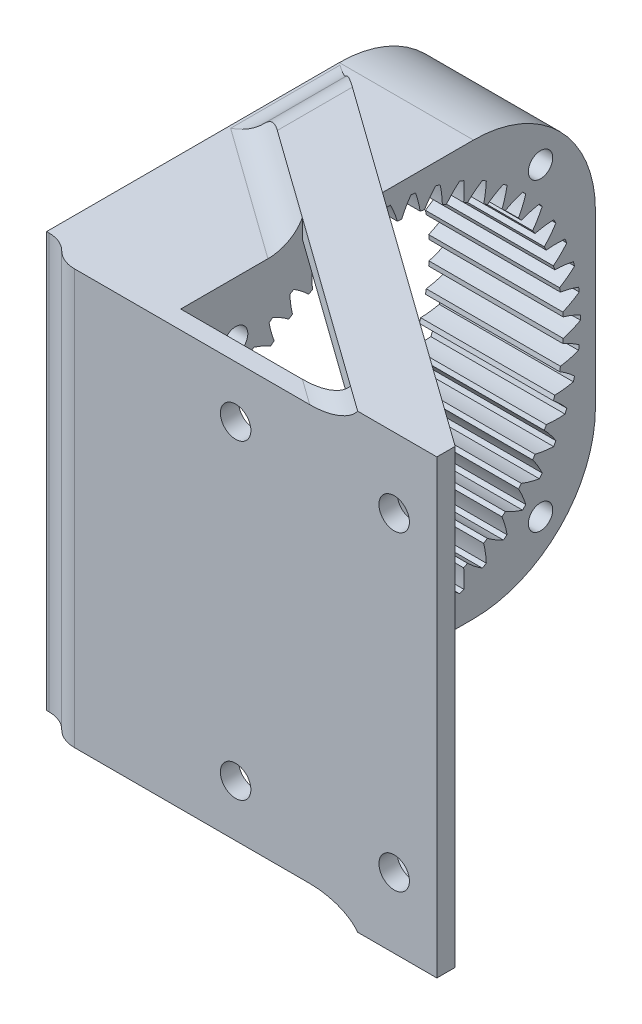
SolidWorks part; units mm, degrees
ref_plane "Plane1" through (0, 0, 0) normal (0, 0, 1) x (1, 0, 0)
ref_plane "Plane2" through (0, 0, 0) normal (0, 1, 0) x (1, 0, 0)
ref_plane "Plane3" through (0, 0, 0) normal (1, 0, 0) x (0, 0, -1)
sketch "HoldingSke" plane through (0, 0, 0) normal (0, 1, 0) x (1, 0, 0)
  line L0 (0, 0) -> (0.5353, -0.5945)
  line L1 (-15, 0) -> (100, 0) construction
  line L2 (0, 0) -> (-2.1039, 2.3779)
  line L3 (0, 0) -> (-11.863, 4.5341)
  line L4 (0, 0) -> (5.7786, 6.4178)
  line L5 (0, 0) -> (-23.7986, -8.8762)
  line L6 (0, 0) -> (-10.5278, -7.1032)
  line L7 (-2.1039, 2.3779) -> (3.3635, 27.1825)
  line L8 (-76.2, 3.6279) -> (-54.61, 3.6279)
  line L9 (-71.009, 38.7566) -> (-53.1078, 45.2721)
  line L10 (-76.2, 71.12) -> (104.1128, 71.12)
  line L11 (0, 0) -> (-12, 0)
  line L12 (-76.2, 101.6) -> (-76.155, 101.6)
  line L13 (24.9733, 27.94) -> (52.9518, 28.4284)
  line L14 (24.9733, 27.94) -> (24.9743, 27.94)
  line L15 (24.9733, 27.94) -> (100.4006, 29.5858)
  circle A0 centre (0, 0) radius 34
  circle A1 centre (0, 0) radius 12.7
  circle A2 centre (0, 0) radius 12.7
  point P27 (0, 0)
  dimension "MHD" = 25.4
  dimension "Hub_dia" = 25.4
  dimension "Diameter" = 68
  dimension "Num_teeth" = 48
  dimension "Pitch" = 0.8
  dimension "Overall_len" = 25.4
  dimension "Show_teeth" = 48
  dimension "Thickness" = 12.7
  dimension "OAL" = 25.4001
  dimension "T_dim" = 21.59
  dimension "Ap" = 20
  dimension "H" = 19.05
  dimension "Pitch_radius" = 180.3128
  dimension "Width" = 12
  dimension "Backlash" = 0.045
  dimension "Addendum_fac" = 1
  dimension "Dedendum_fac" = 1.25
  dimension "Clearance_fac" = 0.25
  dimension "Dedendum_add" = 0.001
  dimension "Module" = 1.25
sketch "BasProSke" plane through (0, 0, 0) normal (0, 1, 0) x (1, 0, 0)
  line L0 (-10, 0) -> (60, 0) construction
  line L1 (0, 28.75) -> (0, 34)
  line L2 (0, 28.75) -> (12, 28.75)
  line L3 (12, 28.75) -> (12, 34)
  line L4 (12, 34) -> (0, 34)
  dimension "Diameter" = 68
  dimension "Thickness" = 12
  dimension "Inside_diameter" = 57.5
revolve "Base-Revolve" add sketch "BasProSke" angle 360 about L0
sketch "TooCutSke" plane through (0, 0, 0) normal (1, 0, 0) x (0, 0, -1)
  line L3 (1.0941, 29.98) -> (1.0941, 53.6633) construction
  line L4 (0, 0) -> (0, 59.563) construction
  line L5 (0, 0) -> (-4.4688, 68.1812) construction
  line L6 (-12.9004, 24.5806) -> (36.1024, 27.7924) construction
  circle A0 centre (0, 0) radius 30 construction
  circle A1 centre (0, 0) radius 31.5635 construction
  circle A2 centre (0, 0) radius 25.3717 construction
  circle A3 centre (0, 0) radius 28.7246 construction
  arc A4 (1.5274, 28.684) -> (0.3763, 31.5613) centre (-12.9004, 24.5806) ccw
  arc A5 (1.5274, 28.684) -> (-1.5274, 28.684) centre (0, 0) ccw
  arc A6 (0.3763, 31.5613) -> (-0.3763, 31.5613) centre (0, 0) ccw
  arc A7 (-0.3763, 31.5613) -> (-1.5274, 28.684) centre (12.9004, 24.5806) ccw
  dimension "Pitch_dia" = 60
  dimension "Base_dia" = 50.7434
  dimension "Root_dia" = 63.127
  dimension "Overcut_dia" = 57.4492
  dimension "Flank_rad" = 15
  dimension "Half_ang" = 3.75
  dimension "Half_CT" = 1.0941
extrude "ToothCut" cut sketch "TooCutSke" along normal through all
fillet "Breaks" [suppressed] radius 0.125
fillet "RootFillets" [suppressed] radius 0.3135
pattern_circular "TeethCuts" count 48 every 7.5 about axis through (-10, 0, 0) along (1, 0, 0) of "RootFillets", "Breaks", "ToothCut"
sketch "Sketch1" plane through (0, 0, 0) normal (-1, 0, 0) x (0, 0, 1)
  line L1 (-34, -34) -> (34, -34)
  line L2 (-34, -34) -> (-34, 34)
  line L3 (-34, 34) -> (34, 34)
  line L4 (34, -34) -> (34, 34)
  line L5 (-34, -34) -> (34, 34) construction
  line L6 (-34, 34) -> (34, -34) construction
  circle A0 centre (0, 0) radius 34 construction
  circle A1 centre (0, 0) radius 34
  point P0 (0, 0)
extrude "Boss-Extrude1" add sketch "Sketch1" against normal up to surface (12 mm away) contours A1 L4 L3 | A1 L3 L2 | A1 L1 L4 | A1 L2 L1 region at (0, -26.4055, -26.4055) region at (0, -26.4055, 26.4055) region at (0, 26.4055, -26.4055) region at (0, 26.4055, 26.4055) up to face at (12, 0, 34)
sketch "Sketch3" plane through (12, 0, 0) normal (1, 0, 0) x (0, 0, -1)
  line L0 (-34, 34) -> (34, 34) construction
  line L1 (25, -25) -> (-25, -25) construction
  line L2 (25, -25) -> (25, 25) construction
  line L3 (25, 25) -> (-25, 25) construction
  line L4 (-25, -25) -> (-25, 25) construction
  line L5 (25, -25) -> (-25, 25) construction
  line L6 (25, 25) -> (-25, -25) construction
  circle A0 centre (-25, -25) radius 2
  circle A1 centre (-25, 25) radius 2
  circle A2 centre (25, 25) radius 2
  circle A3 centre (25, -25) radius 2
  point P0 (0, 0)
  dimension "D2" = 4
  dimension "D1" = 9
extrude "Cut-Extrude1" cut sketch "Sketch3" against normal through all
sketch "Sketch4" plane through (12, 0, 0) normal (1, 0, 0) x (0, 0, -1)
  line L1 (-34, -34) -> (34, -34)
  line L2 (-34, -34) -> (-34, 34)
  line L3 (-34, 34) -> (34, 34)
  line L4 (34, -34) -> (34, 34)
  circle A1 centre (-25, -25) radius 2
  circle A2 centre (-25, -25) radius 2
  circle A3 centre (-25, 25) radius 2
  circle A4 centre (-25, 25) radius 2
  circle A5 centre (25, 25) radius 2
  circle A6 centre (25, 25) radius 2
  circle A7 centre (25, -25) radius 2
  circle A8 centre (25, -25) radius 2
  arc A192 (3.7465, 31.3404) -> (2.2403, 28.6626) centre (15.9985, 22.6865) ccw
  arc A193 (4.4926, 31.2421) -> (3.7465, 31.3404) centre (0, 0) ccw
  arc A194 (5.2544, 28.2658) -> (4.4926, 31.2421) centre (-9.5817, 26.0542) ccw
  arc A195 (5.9624, 28.1249) -> (5.2544, 28.2658) centre (0, 0) ccw
  arc A196 (7.8052, 30.5832) -> (5.9624, 28.1249) centre (18.8228, 20.4042) ccw
  arc A197 (8.5321, 30.3885) -> (7.8052, 30.5832) centre (0, 0) ccw
  arc A198 (8.8989, 27.3381) -> (8.5321, 30.3885) centre (-6.0989, 27.0819) ccw
  arc A199 (9.5824, 27.1061) -> (8.8989, 27.3381) centre (0, 0) ccw
  arc A200 (11.7304, 29.3028) -> (9.5824, 27.1061) centre (21.325, 17.7727) ccw
  arc A201 (12.4256, 29.0148) -> (11.7304, 29.3028) centre (0, 0) ccw
  arc A202 (12.3911, 25.9427) -> (12.4256, 29.0148) centre (-2.5119, 27.6463) ccw
  arc A203 (13.0385, 25.6234) -> (12.3911, 25.9427) centre (0, 0) ccw
  arc A204 (15.4548, 27.521) -> (13.0385, 25.6234) centre (23.4624, 14.8372) ccw
  arc A205 (16.1065, 27.1447) -> (15.4548, 27.521) centre (0, 0) ccw
  arc A206 (15.6713, 24.1034) -> (16.1065, 27.1447) centre (1.1182, 27.7376) ccw
  arc A207 (16.2715, 23.7023) -> (15.6713, 24.1034) centre (0, 0) ccw
  arc A208 (18.9148, 25.2683) -> (16.2715, 23.7023) centre (25.1983, 11.6478) ccw
  arc A209 (19.5118, 24.8102) -> (18.9148, 25.2683) centre (0, 0) ccw
  arc A210 (18.6833, 21.8517) -> (19.5118, 24.8102) centre (4.7291, 27.3544) ccw
  arc A211 (19.2261, 21.3757) -> (18.6833, 21.8517) centre (0, 0) ccw
  arc A212 (22.0511, 22.5832) -> (19.2261, 21.3757) centre (26.5031, 8.2591) ccw
  arc A213 (22.5832, 22.0511) -> (22.0511, 22.5832) centre (0, 0) ccw
  arc A214 (21.3757, 19.2261) -> (22.5832, 22.0511) centre (8.2591, 26.5031) ccw
  arc A215 (21.8517, 18.6833) -> (21.3757, 19.2261) centre (0, 0) ccw
  arc A216 (24.8102, 19.5118) -> (21.8517, 18.6833) centre (27.3544, 4.7291) ccw
  arc A217 (25.2683, 18.9148) -> (24.8102, 19.5118) centre (0, 0) ccw
  arc A218 (23.7023, 16.2715) -> (25.2683, 18.9148) centre (11.6478, 25.1983) ccw
  arc A219 (24.1034, 15.6713) -> (23.7023, 16.2715) centre (0, 0) ccw
  arc A220 (27.1447, 16.1065) -> (24.1034, 15.6713) centre (27.7376, 1.1182) ccw
  arc A221 (27.521, 15.4548) -> (27.1447, 16.1065) centre (0, 0) ccw
  arc A222 (25.6234, 13.0385) -> (27.521, 15.4548) centre (14.8372, 23.4624) ccw
  arc A223 (25.9427, 12.3911) -> (25.6234, 13.0385) centre (0, 0) ccw
  arc A224 (29.0148, 12.4256) -> (25.9427, 12.3911) centre (27.6463, -2.5119) ccw
  arc A225 (29.3028, 11.7304) -> (29.0148, 12.4256) centre (0, 0) ccw
  arc A226 (27.1061, 9.5824) -> (29.3028, 11.7304) centre (17.7727, 21.325) ccw
  arc A227 (27.3381, 8.8989) -> (27.1061, 9.5824) centre (0, 0) ccw
  arc A228 (30.3885, 8.5321) -> (27.3381, 8.8989) centre (27.0819, -6.0989) ccw
  arc A229 (30.5832, 7.8052) -> (30.3885, 8.5321) centre (0, 0) ccw
  arc A230 (28.1249, 5.9624) -> (30.5832, 7.8052) centre (20.4042, 18.8228) ccw
  arc A231 (28.2658, 5.2544) -> (28.1249, 5.9624) centre (0, 0) ccw
  arc A232 (31.2421, 4.4926) -> (28.2658, 5.2544) centre (26.0542, -9.5817) ccw
  arc A233 (31.3404, 3.7465) -> (31.2421, 4.4926) centre (0, 0) ccw
  arc A234 (28.6626, 2.2403) -> (31.3404, 3.7465) centre (22.6865, 15.9985) ccw
  arc A235 (28.7098, 1.52) -> (28.6626, 2.2403) centre (0, 0) ccw
  arc A236 (31.5613, 0.3763) -> (28.7098, 1.52) centre (24.5806, -12.9004) ccw
  arc A237 (31.5613, -0.3763) -> (31.5613, 0.3763) centre (0, 0) ccw
  arc A238 (28.7098, -1.52) -> (31.5613, -0.3763) centre (24.5806, 12.9004) ccw
  arc A239 (28.6626, -2.2403) -> (28.7098, -1.52) centre (0, 0) ccw
  arc A240 (31.3404, -3.7465) -> (28.6626, -2.2403) centre (22.6865, -15.9985) ccw
  arc A241 (31.2421, -4.4926) -> (31.3404, -3.7465) centre (0, 0) ccw
  arc A242 (28.2658, -5.2544) -> (31.2421, -4.4926) centre (26.0542, 9.5817) ccw
  arc A243 (28.1249, -5.9624) -> (28.2658, -5.2544) centre (0, 0) ccw
  arc A244 (30.5832, -7.8052) -> (28.1249, -5.9624) centre (20.4042, -18.8228) ccw
  arc A245 (30.3885, -8.5321) -> (30.5832, -7.8052) centre (0, 0) ccw
  arc A246 (27.3381, -8.8989) -> (30.3885, -8.5321) centre (27.0819, 6.0989) ccw
  arc A247 (27.1061, -9.5824) -> (27.3381, -8.8989) centre (0, 0) ccw
  arc A248 (29.3028, -11.7304) -> (27.1061, -9.5824) centre (17.7727, -21.325) ccw
  arc A249 (29.0148, -12.4256) -> (29.3028, -11.7304) centre (0, 0) ccw
  arc A250 (25.9427, -12.3911) -> (29.0148, -12.4256) centre (27.6463, 2.5119) ccw
  arc A251 (25.6234, -13.0385) -> (25.9427, -12.3911) centre (0, 0) ccw
  arc A252 (27.521, -15.4548) -> (25.6234, -13.0385) centre (14.8372, -23.4624) ccw
  arc A253 (27.1447, -16.1065) -> (27.521, -15.4548) centre (0, 0) ccw
  arc A254 (24.1034, -15.6713) -> (27.1447, -16.1065) centre (27.7376, -1.1182) ccw
  arc A255 (23.7023, -16.2715) -> (24.1034, -15.6713) centre (0, 0) ccw
  arc A256 (25.2683, -18.9148) -> (23.7023, -16.2715) centre (11.6478, -25.1983) ccw
  arc A257 (24.8102, -19.5118) -> (25.2683, -18.9148) centre (0, 0) ccw
  arc A258 (21.8517, -18.6833) -> (24.8102, -19.5118) centre (27.3544, -4.7291) ccw
  arc A259 (21.3757, -19.2261) -> (21.8517, -18.6833) centre (0, 0) ccw
  arc A260 (22.5832, -22.0511) -> (21.3757, -19.2261) centre (8.2591, -26.5031) ccw
  arc A261 (22.0511, -22.5832) -> (22.5832, -22.0511) centre (0, 0) ccw
  arc A262 (19.2261, -21.3757) -> (22.0511, -22.5832) centre (26.5031, -8.2591) ccw
  arc A263 (18.6833, -21.8517) -> (19.2261, -21.3757) centre (0, 0) ccw
  arc A264 (19.5118, -24.8102) -> (18.6833, -21.8517) centre (4.7291, -27.3544) ccw
  arc A265 (18.9148, -25.2683) -> (19.5118, -24.8102) centre (0, 0) ccw
  arc A266 (16.2715, -23.7023) -> (18.9148, -25.2683) centre (25.1983, -11.6478) ccw
  arc A267 (15.6713, -24.1034) -> (16.2715, -23.7023) centre (0, 0) ccw
  arc A268 (16.1065, -27.1447) -> (15.6713, -24.1034) centre (1.1182, -27.7376) ccw
  arc A269 (15.4548, -27.521) -> (16.1065, -27.1447) centre (0, 0) ccw
  arc A270 (13.0385, -25.6234) -> (15.4548, -27.521) centre (23.4624, -14.8372) ccw
  arc A271 (12.3911, -25.9427) -> (13.0385, -25.6234) centre (0, 0) ccw
  arc A272 (12.4256, -29.0148) -> (12.3911, -25.9427) centre (-2.5119, -27.6463) ccw
  arc A273 (11.7304, -29.3028) -> (12.4256, -29.0148) centre (0, 0) ccw
  arc A274 (9.5824, -27.1061) -> (11.7304, -29.3028) centre (21.325, -17.7727) ccw
  arc A275 (8.8989, -27.3381) -> (9.5824, -27.1061) centre (0, 0) ccw
  arc A276 (8.5321, -30.3885) -> (8.8989, -27.3381) centre (-6.0989, -27.0819) ccw
  arc A277 (7.8052, -30.5832) -> (8.5321, -30.3885) centre (0, 0) ccw
  arc A278 (5.9624, -28.1249) -> (7.8052, -30.5832) centre (18.8228, -20.4042) ccw
  arc A279 (5.2544, -28.2658) -> (5.9624, -28.1249) centre (0, 0) ccw
  arc A280 (4.4926, -31.2421) -> (5.2544, -28.2658) centre (-9.5817, -26.0542) ccw
  arc A281 (3.7465, -31.3404) -> (4.4926, -31.2421) centre (0, 0) ccw
  arc A282 (2.2403, -28.6626) -> (3.7465, -31.3404) centre (15.9985, -22.6865) ccw
  arc A283 (1.52, -28.7098) -> (2.2403, -28.6626) centre (0, 0) ccw
  arc A284 (0.3763, -31.5613) -> (1.52, -28.7098) centre (-12.9004, -24.5806) ccw
  arc A285 (-0.3763, -31.5613) -> (0.3763, -31.5613) centre (0, 0) ccw
  arc A286 (-1.52, -28.7098) -> (-0.3763, -31.5613) centre (12.9004, -24.5806) ccw
  arc A287 (-2.2403, -28.6626) -> (-1.52, -28.7098) centre (0, 0) ccw
  arc A288 (-3.7465, -31.3404) -> (-2.2403, -28.6626) centre (-15.9985, -22.6865) ccw
  arc A289 (-4.4926, -31.2421) -> (-3.7465, -31.3404) centre (0, 0) ccw
  arc A290 (-5.2544, -28.2658) -> (-4.4926, -31.2421) centre (9.5817, -26.0542) ccw
  arc A291 (-5.9624, -28.1249) -> (-5.2544, -28.2658) centre (0, 0) ccw
  arc A292 (-7.8052, -30.5832) -> (-5.9624, -28.1249) centre (-18.8228, -20.4042) ccw
  arc A293 (-8.5321, -30.3885) -> (-7.8052, -30.5832) centre (0, 0) ccw
  arc A294 (-8.8989, -27.3381) -> (-8.5321, -30.3885) centre (6.0989, -27.0819) ccw
  arc A295 (-9.5824, -27.1061) -> (-8.8989, -27.3381) centre (0, 0) ccw
  arc A296 (-11.7304, -29.3028) -> (-9.5824, -27.1061) centre (-21.325, -17.7727) ccw
  arc A297 (-12.4256, -29.0148) -> (-11.7304, -29.3028) centre (0, 0) ccw
  arc A298 (-12.3911, -25.9427) -> (-12.4256, -29.0148) centre (2.5119, -27.6463) ccw
  arc A299 (-13.0385, -25.6234) -> (-12.3911, -25.9427) centre (0, 0) ccw
  arc A300 (-15.4548, -27.521) -> (-13.0385, -25.6234) centre (-23.4624, -14.8372) ccw
  arc A301 (-16.1065, -27.1447) -> (-15.4548, -27.521) centre (0, 0) ccw
  arc A302 (-15.6713, -24.1034) -> (-16.1065, -27.1447) centre (-1.1182, -27.7376) ccw
  arc A303 (-16.2715, -23.7023) -> (-15.6713, -24.1034) centre (0, 0) ccw
  arc A304 (-18.9148, -25.2683) -> (-16.2715, -23.7023) centre (-25.1983, -11.6478) ccw
  arc A305 (-19.5118, -24.8102) -> (-18.9148, -25.2683) centre (0, 0) ccw
  arc A306 (-18.6833, -21.8517) -> (-19.5118, -24.8102) centre (-4.7291, -27.3544) ccw
  arc A307 (-19.2261, -21.3757) -> (-18.6833, -21.8517) centre (0, 0) ccw
  arc A308 (-22.0511, -22.5832) -> (-19.2261, -21.3757) centre (-26.5031, -8.2591) ccw
  arc A309 (-22.5832, -22.0511) -> (-22.0511, -22.5832) centre (0, 0) ccw
  arc A310 (-21.3757, -19.2261) -> (-22.5832, -22.0511) centre (-8.2591, -26.5031) ccw
  arc A311 (-21.8517, -18.6833) -> (-21.3757, -19.2261) centre (0, 0) ccw
  arc A312 (-24.8102, -19.5118) -> (-21.8517, -18.6833) centre (-27.3544, -4.7291) ccw
  arc A313 (-25.2683, -18.9148) -> (-24.8102, -19.5118) centre (0, 0) ccw
  arc A314 (-23.7023, -16.2715) -> (-25.2683, -18.9148) centre (-11.6478, -25.1983) ccw
  arc A315 (-24.1034, -15.6713) -> (-23.7023, -16.2715) centre (0, 0) ccw
  arc A316 (-27.1447, -16.1065) -> (-24.1034, -15.6713) centre (-27.7376, -1.1182) ccw
  arc A317 (-27.521, -15.4548) -> (-27.1447, -16.1065) centre (0, 0) ccw
  arc A318 (-25.6234, -13.0385) -> (-27.521, -15.4548) centre (-14.8372, -23.4624) ccw
  arc A319 (-25.9427, -12.3911) -> (-25.6234, -13.0385) centre (0, 0) ccw
  arc A320 (-29.0148, -12.4256) -> (-25.9427, -12.3911) centre (-27.6463, 2.5119) ccw
  arc A321 (-29.3028, -11.7304) -> (-29.0148, -12.4256) centre (0, 0) ccw
  arc A322 (-27.1061, -9.5824) -> (-29.3028, -11.7304) centre (-17.7727, -21.325) ccw
  arc A323 (-27.3381, -8.8989) -> (-27.1061, -9.5824) centre (0, 0) ccw
  arc A324 (-30.3885, -8.5321) -> (-27.3381, -8.8989) centre (-27.0819, 6.0989) ccw
  arc A325 (-30.5832, -7.8052) -> (-30.3885, -8.5321) centre (0, 0) ccw
  arc A326 (-28.1249, -5.9624) -> (-30.5832, -7.8052) centre (-20.4042, -18.8228) ccw
  arc A327 (-28.2658, -5.2544) -> (-28.1249, -5.9624) centre (0, 0) ccw
  arc A328 (-31.2421, -4.4926) -> (-28.2658, -5.2544) centre (-26.0542, 9.5817) ccw
  arc A329 (-31.3404, -3.7465) -> (-31.2421, -4.4926) centre (0, 0) ccw
  arc A330 (-28.6626, -2.2403) -> (-31.3404, -3.7465) centre (-22.6865, -15.9985) ccw
  arc A331 (-28.7098, -1.52) -> (-28.6626, -2.2403) centre (0, 0) ccw
  arc A332 (-31.5613, -0.3763) -> (-28.7098, -1.52) centre (-24.5806, 12.9004) ccw
  arc A333 (-31.5613, 0.3763) -> (-31.5613, -0.3763) centre (0, 0) ccw
  arc A334 (-28.7098, 1.52) -> (-31.5613, 0.3763) centre (-24.5806, -12.9004) ccw
  arc A335 (-28.6626, 2.2403) -> (-28.7098, 1.52) centre (0, 0) ccw
  arc A336 (-31.3404, 3.7465) -> (-28.6626, 2.2403) centre (-22.6865, 15.9985) ccw
  arc A337 (-31.2421, 4.4926) -> (-31.3404, 3.7465) centre (0, 0) ccw
  arc A338 (-28.2658, 5.2544) -> (-31.2421, 4.4926) centre (-26.0542, -9.5817) ccw
  arc A339 (-28.1249, 5.9624) -> (-28.2658, 5.2544) centre (0, 0) ccw
  arc A340 (-30.5832, 7.8052) -> (-28.1249, 5.9624) centre (-20.4042, 18.8228) ccw
  arc A341 (-30.3885, 8.5321) -> (-30.5832, 7.8052) centre (0, 0) ccw
  arc A342 (-27.3381, 8.8989) -> (-30.3885, 8.5321) centre (-27.0819, -6.0989) ccw
  arc A343 (-27.1061, 9.5824) -> (-27.3381, 8.8989) centre (0, 0) ccw
  arc A344 (-29.3028, 11.7304) -> (-27.1061, 9.5824) centre (-17.7727, 21.325) ccw
  arc A345 (-29.0148, 12.4256) -> (-29.3028, 11.7304) centre (0, 0) ccw
  arc A346 (-25.9427, 12.3911) -> (-29.0148, 12.4256) centre (-27.6463, -2.5119) ccw
  arc A347 (-25.6234, 13.0385) -> (-25.9427, 12.3911) centre (0, 0) ccw
  arc A348 (-27.521, 15.4548) -> (-25.6234, 13.0385) centre (-14.8372, 23.4624) ccw
  arc A349 (-27.1447, 16.1065) -> (-27.521, 15.4548) centre (0, 0) ccw
  arc A350 (-24.1034, 15.6713) -> (-27.1447, 16.1065) centre (-27.7376, 1.1182) ccw
  arc A351 (-23.7023, 16.2715) -> (-24.1034, 15.6713) centre (0, 0) ccw
  arc A352 (-25.2683, 18.9148) -> (-23.7023, 16.2715) centre (-11.6478, 25.1983) ccw
  arc A353 (-24.8102, 19.5118) -> (-25.2683, 18.9148) centre (0, 0) ccw
  arc A354 (-21.8517, 18.6833) -> (-24.8102, 19.5118) centre (-27.3544, 4.7291) ccw
  arc A355 (-21.3757, 19.2261) -> (-21.8517, 18.6833) centre (0, 0) ccw
  arc A356 (-22.5832, 22.0511) -> (-21.3757, 19.2261) centre (-8.2591, 26.5031) ccw
  arc A357 (-22.0511, 22.5832) -> (-22.5832, 22.0511) centre (0, 0) ccw
  arc A358 (-19.2261, 21.3757) -> (-22.0511, 22.5832) centre (-26.5031, 8.2591) ccw
  arc A359 (-18.6833, 21.8517) -> (-19.2261, 21.3757) centre (0, 0) ccw
  arc A360 (-19.5118, 24.8102) -> (-18.6833, 21.8517) centre (-4.7291, 27.3544) ccw
  arc A361 (-18.9148, 25.2683) -> (-19.5118, 24.8102) centre (0, 0) ccw
  arc A362 (-16.2715, 23.7023) -> (-18.9148, 25.2683) centre (-25.1983, 11.6478) ccw
  arc A363 (-15.6713, 24.1034) -> (-16.2715, 23.7023) centre (0, 0) ccw
  arc A364 (-16.1065, 27.1447) -> (-15.6713, 24.1034) centre (-1.1182, 27.7376) ccw
  arc A365 (-15.4548, 27.521) -> (-16.1065, 27.1447) centre (0, 0) ccw
  arc A366 (-13.0385, 25.6234) -> (-15.4548, 27.521) centre (-23.4624, 14.8372) ccw
  arc A367 (-12.3911, 25.9427) -> (-13.0385, 25.6234) centre (0, 0) ccw
  arc A368 (-12.4256, 29.0148) -> (-12.3911, 25.9427) centre (2.5119, 27.6463) ccw
  arc A369 (-11.7304, 29.3028) -> (-12.4256, 29.0148) centre (0, 0) ccw
  arc A370 (-9.5824, 27.1061) -> (-11.7304, 29.3028) centre (-21.325, 17.7727) ccw
  arc A371 (-8.8989, 27.3381) -> (-9.5824, 27.1061) centre (0, 0) ccw
  arc A372 (-8.5321, 30.3885) -> (-8.8989, 27.3381) centre (6.0989, 27.0819) ccw
  arc A373 (-7.8052, 30.5832) -> (-8.5321, 30.3885) centre (0, 0) ccw
  arc A374 (-5.9624, 28.1249) -> (-7.8052, 30.5832) centre (-18.8228, 20.4042) ccw
  arc A375 (-5.2544, 28.2658) -> (-5.9624, 28.1249) centre (0, 0) ccw
  arc A376 (-4.4926, 31.2421) -> (-5.2544, 28.2658) centre (9.5817, 26.0542) ccw
  arc A377 (-3.7465, 31.3404) -> (-4.4926, 31.2421) centre (0, 0) ccw
  arc A378 (-2.2403, 28.6626) -> (-3.7465, 31.3404) centre (-15.9985, 22.6865) ccw
  arc A379 (-1.52, 28.7098) -> (-2.2403, 28.6626) centre (0, 0) ccw
  arc A380 (-0.3763, 31.5613) -> (-1.52, 28.7098) centre (12.9004, 24.5806) ccw
  arc A381 (0.3763, 31.5613) -> (-0.3763, 31.5613) centre (0, 0) ccw
  arc A382 (1.52, 28.7098) -> (0.3763, 31.5613) centre (-12.9004, 24.5806) ccw
  arc A383 (2.2403, 28.6626) -> (1.52, 28.7098) centre (0, 0) ccw
  arc A384 (3.7465, 31.3404) -> (2.2403, 28.6626) centre (15.9985, 22.6865) ccw
  arc A385 (4.4926, 31.2421) -> (3.7465, 31.3404) centre (0, 0) ccw
  arc A386 (5.2544, 28.2658) -> (4.4926, 31.2421) centre (-9.5817, 26.0542) ccw
  arc A387 (5.9624, 28.1249) -> (5.2544, 28.2658) centre (0, 0) ccw
  arc A388 (7.8052, 30.5832) -> (5.9624, 28.1249) centre (18.8228, 20.4042) ccw
  arc A389 (8.5321, 30.3885) -> (7.8052, 30.5832) centre (0, 0) ccw
  arc A390 (8.8989, 27.3381) -> (8.5321, 30.3885) centre (-6.0989, 27.0819) ccw
  arc A391 (9.5824, 27.1061) -> (8.8989, 27.3381) centre (0, 0) ccw
  arc A392 (11.7304, 29.3028) -> (9.5824, 27.1061) centre (21.325, 17.7727) ccw
  arc A393 (12.4256, 29.0148) -> (11.7304, 29.3028) centre (0, 0) ccw
  arc A394 (12.3911, 25.9427) -> (12.4256, 29.0148) centre (-2.5119, 27.6463) ccw
  arc A395 (13.0385, 25.6234) -> (12.3911, 25.9427) centre (0, 0) ccw
  arc A396 (15.4548, 27.521) -> (13.0385, 25.6234) centre (23.4624, 14.8372) ccw
  arc A397 (16.1065, 27.1447) -> (15.4548, 27.521) centre (0, 0) ccw
  arc A398 (15.6713, 24.1034) -> (16.1065, 27.1447) centre (1.1182, 27.7376) ccw
  arc A399 (16.2715, 23.7023) -> (15.6713, 24.1034) centre (0, 0) ccw
  arc A400 (18.9148, 25.2683) -> (16.2715, 23.7023) centre (25.1983, 11.6478) ccw
  arc A401 (19.5118, 24.8102) -> (18.9148, 25.2683) centre (0, 0) ccw
  arc A402 (18.6833, 21.8517) -> (19.5118, 24.8102) centre (4.7291, 27.3544) ccw
  arc A403 (19.2261, 21.3757) -> (18.6833, 21.8517) centre (0, 0) ccw
  arc A404 (22.0511, 22.5832) -> (19.2261, 21.3757) centre (26.5031, 8.2591) ccw
  arc A405 (22.5832, 22.0511) -> (22.0511, 22.5832) centre (0, 0) ccw
  arc A406 (21.3757, 19.2261) -> (22.5832, 22.0511) centre (8.2591, 26.5031) ccw
  arc A407 (21.8517, 18.6833) -> (21.3757, 19.2261) centre (0, 0) ccw
  arc A408 (24.8102, 19.5118) -> (21.8517, 18.6833) centre (27.3544, 4.7291) ccw
  arc A409 (25.2683, 18.9148) -> (24.8102, 19.5118) centre (0, 0) ccw
  arc A410 (23.7023, 16.2715) -> (25.2683, 18.9148) centre (11.6478, 25.1983) ccw
  arc A411 (24.1034, 15.6713) -> (23.7023, 16.2715) centre (0, 0) ccw
  arc A412 (27.1447, 16.1065) -> (24.1034, 15.6713) centre (27.7376, 1.1182) ccw
  arc A413 (27.521, 15.4548) -> (27.1447, 16.1065) centre (0, 0) ccw
  arc A414 (25.6234, 13.0385) -> (27.521, 15.4548) centre (14.8372, 23.4624) ccw
  arc A415 (25.9427, 12.3911) -> (25.6234, 13.0385) centre (0, 0) ccw
  arc A416 (29.0148, 12.4256) -> (25.9427, 12.3911) centre (27.6463, -2.5119) ccw
  arc A417 (29.3028, 11.7304) -> (29.0148, 12.4256) centre (0, 0) ccw
  arc A418 (27.1061, 9.5824) -> (29.3028, 11.7304) centre (17.7727, 21.325) ccw
  arc A419 (27.3381, 8.8989) -> (27.1061, 9.5824) centre (0, 0) ccw
  arc A420 (30.3885, 8.5321) -> (27.3381, 8.8989) centre (27.0819, -6.0989) ccw
  arc A421 (30.5832, 7.8052) -> (30.3885, 8.5321) centre (0, 0) ccw
  arc A422 (28.1249, 5.9624) -> (30.5832, 7.8052) centre (20.4042, 18.8228) ccw
  arc A423 (28.2658, 5.2544) -> (28.1249, 5.9624) centre (0, 0) ccw
  arc A424 (31.2421, 4.4926) -> (28.2658, 5.2544) centre (26.0542, -9.5817) ccw
  arc A425 (31.3404, 3.7465) -> (31.2421, 4.4926) centre (0, 0) ccw
  arc A426 (28.6626, 2.2403) -> (31.3404, 3.7465) centre (22.6865, 15.9985) ccw
  arc A427 (28.7098, 1.52) -> (28.6626, 2.2403) centre (0, 0) ccw
  arc A428 (31.5613, 0.3763) -> (28.7098, 1.52) centre (24.5806, -12.9004) ccw
  arc A429 (31.5613, -0.3763) -> (31.5613, 0.3763) centre (0, 0) ccw
  arc A430 (28.7098, -1.52) -> (31.5613, -0.3763) centre (24.5806, 12.9004) ccw
  arc A431 (28.6626, -2.2403) -> (28.7098, -1.52) centre (0, 0) ccw
  arc A432 (31.3404, -3.7465) -> (28.6626, -2.2403) centre (22.6865, -15.9985) ccw
  arc A433 (31.2421, -4.4926) -> (31.3404, -3.7465) centre (0, 0) ccw
  arc A434 (28.2658, -5.2544) -> (31.2421, -4.4926) centre (26.0542, 9.5817) ccw
  arc A435 (28.1249, -5.9624) -> (28.2658, -5.2544) centre (0, 0) ccw
  arc A436 (30.5832, -7.8052) -> (28.1249, -5.9624) centre (20.4042, -18.8228) ccw
  arc A437 (30.3885, -8.5321) -> (30.5832, -7.8052) centre (0, 0) ccw
  arc A438 (27.3381, -8.8989) -> (30.3885, -8.5321) centre (27.0819, 6.0989) ccw
  arc A439 (27.1061, -9.5824) -> (27.3381, -8.8989) centre (0, 0) ccw
  arc A440 (29.3028, -11.7304) -> (27.1061, -9.5824) centre (17.7727, -21.325) ccw
  arc A441 (29.0148, -12.4256) -> (29.3028, -11.7304) centre (0, 0) ccw
  arc A442 (25.9427, -12.3911) -> (29.0148, -12.4256) centre (27.6463, 2.5119) ccw
  arc A443 (25.6234, -13.0385) -> (25.9427, -12.3911) centre (0, 0) ccw
  arc A444 (27.521, -15.4548) -> (25.6234, -13.0385) centre (14.8372, -23.4624) ccw
  arc A445 (27.1447, -16.1065) -> (27.521, -15.4548) centre (0, 0) ccw
  arc A446 (24.1034, -15.6713) -> (27.1447, -16.1065) centre (27.7376, -1.1182) ccw
  arc A447 (23.7023, -16.2715) -> (24.1034, -15.6713) centre (0, 0) ccw
  arc A448 (25.2683, -18.9148) -> (23.7023, -16.2715) centre (11.6478, -25.1983) ccw
  arc A449 (24.8102, -19.5118) -> (25.2683, -18.9148) centre (0, 0) ccw
  arc A450 (21.8517, -18.6833) -> (24.8102, -19.5118) centre (27.3544, -4.7291) ccw
  arc A451 (21.3757, -19.2261) -> (21.8517, -18.6833) centre (0, 0) ccw
  arc A452 (22.5832, -22.0511) -> (21.3757, -19.2261) centre (8.2591, -26.5031) ccw
  arc A453 (22.0511, -22.5832) -> (22.5832, -22.0511) centre (0, 0) ccw
  arc A454 (19.2261, -21.3757) -> (22.0511, -22.5832) centre (26.5031, -8.2591) ccw
  arc A455 (18.6833, -21.8517) -> (19.2261, -21.3757) centre (0, 0) ccw
  arc A456 (19.5118, -24.8102) -> (18.6833, -21.8517) centre (4.7291, -27.3544) ccw
  arc A457 (18.9148, -25.2683) -> (19.5118, -24.8102) centre (0, 0) ccw
  arc A458 (16.2715, -23.7023) -> (18.9148, -25.2683) centre (25.1983, -11.6478) ccw
  arc A459 (15.6713, -24.1034) -> (16.2715, -23.7023) centre (0, 0) ccw
  arc A460 (16.1065, -27.1447) -> (15.6713, -24.1034) centre (1.1182, -27.7376) ccw
  arc A461 (15.4548, -27.521) -> (16.1065, -27.1447) centre (0, 0) ccw
  arc A462 (13.0385, -25.6234) -> (15.4548, -27.521) centre (23.4624, -14.8372) ccw
  arc A463 (12.3911, -25.9427) -> (13.0385, -25.6234) centre (0, 0) ccw
  arc A464 (12.4256, -29.0148) -> (12.3911, -25.9427) centre (-2.5119, -27.6463) ccw
  arc A465 (11.7304, -29.3028) -> (12.4256, -29.0148) centre (0, 0) ccw
  arc A466 (9.5824, -27.1061) -> (11.7304, -29.3028) centre (21.325, -17.7727) ccw
  arc A467 (8.8989, -27.3381) -> (9.5824, -27.1061) centre (0, 0) ccw
  arc A468 (8.5321, -30.3885) -> (8.8989, -27.3381) centre (-6.0989, -27.0819) ccw
  arc A469 (7.8052, -30.5832) -> (8.5321, -30.3885) centre (0, 0) ccw
  arc A470 (5.9624, -28.1249) -> (7.8052, -30.5832) centre (18.8228, -20.4042) ccw
  arc A471 (5.2544, -28.2658) -> (5.9624, -28.1249) centre (0, 0) ccw
  arc A472 (4.4926, -31.2421) -> (5.2544, -28.2658) centre (-9.5817, -26.0542) ccw
  arc A473 (3.7465, -31.3404) -> (4.4926, -31.2421) centre (0, 0) ccw
  arc A474 (2.2403, -28.6626) -> (3.7465, -31.3404) centre (15.9985, -22.6865) ccw
  arc A475 (1.52, -28.7098) -> (2.2403, -28.6626) centre (0, 0) ccw
  arc A476 (0.3763, -31.5613) -> (1.52, -28.7098) centre (-12.9004, -24.5806) ccw
  arc A477 (-0.3763, -31.5613) -> (0.3763, -31.5613) centre (0, 0) ccw
  arc A478 (-1.52, -28.7098) -> (-0.3763, -31.5613) centre (12.9004, -24.5806) ccw
  arc A479 (-2.2403, -28.6626) -> (-1.52, -28.7098) centre (0, 0) ccw
  arc A480 (-3.7465, -31.3404) -> (-2.2403, -28.6626) centre (-15.9985, -22.6865) ccw
  arc A481 (-4.4926, -31.2421) -> (-3.7465, -31.3404) centre (0, 0) ccw
  arc A482 (-5.2544, -28.2658) -> (-4.4926, -31.2421) centre (9.5817, -26.0542) ccw
  arc A483 (-5.9624, -28.1249) -> (-5.2544, -28.2658) centre (0, 0) ccw
  arc A484 (-7.8052, -30.5832) -> (-5.9624, -28.1249) centre (-18.8228, -20.4042) ccw
  arc A485 (-8.5321, -30.3885) -> (-7.8052, -30.5832) centre (0, 0) ccw
  arc A486 (-8.8989, -27.3381) -> (-8.5321, -30.3885) centre (6.0989, -27.0819) ccw
  arc A487 (-9.5824, -27.1061) -> (-8.8989, -27.3381) centre (0, 0) ccw
  arc A488 (-11.7304, -29.3028) -> (-9.5824, -27.1061) centre (-21.325, -17.7727) ccw
  arc A489 (-12.4256, -29.0148) -> (-11.7304, -29.3028) centre (0, 0) ccw
  arc A490 (-12.3911, -25.9427) -> (-12.4256, -29.0148) centre (2.5119, -27.6463) ccw
  arc A491 (-13.0385, -25.6234) -> (-12.3911, -25.9427) centre (0, 0) ccw
  arc A492 (-15.4548, -27.521) -> (-13.0385, -25.6234) centre (-23.4624, -14.8372) ccw
  arc A493 (-16.1065, -27.1447) -> (-15.4548, -27.521) centre (0, 0) ccw
  arc A494 (-15.6713, -24.1034) -> (-16.1065, -27.1447) centre (-1.1182, -27.7376) ccw
  arc A495 (-16.2715, -23.7023) -> (-15.6713, -24.1034) centre (0, 0) ccw
  arc A496 (-18.9148, -25.2683) -> (-16.2715, -23.7023) centre (-25.1983, -11.6478) ccw
  arc A497 (-19.5118, -24.8102) -> (-18.9148, -25.2683) centre (0, 0) ccw
  arc A498 (-18.6833, -21.8517) -> (-19.5118, -24.8102) centre (-4.7291, -27.3544) ccw
  arc A499 (-19.2261, -21.3757) -> (-18.6833, -21.8517) centre (0, 0) ccw
  arc A500 (-22.0511, -22.5832) -> (-19.2261, -21.3757) centre (-26.5031, -8.2591) ccw
  arc A501 (-22.5832, -22.0511) -> (-22.0511, -22.5832) centre (0, 0) ccw
  arc A502 (-21.3757, -19.2261) -> (-22.5832, -22.0511) centre (-8.2591, -26.5031) ccw
  arc A503 (-21.8517, -18.6833) -> (-21.3757, -19.2261) centre (0, 0) ccw
  arc A504 (-24.8102, -19.5118) -> (-21.8517, -18.6833) centre (-27.3544, -4.7291) ccw
  arc A505 (-25.2683, -18.9148) -> (-24.8102, -19.5118) centre (0, 0) ccw
  arc A506 (-23.7023, -16.2715) -> (-25.2683, -18.9148) centre (-11.6478, -25.1983) ccw
  arc A507 (-24.1034, -15.6713) -> (-23.7023, -16.2715) centre (0, 0) ccw
  arc A508 (-27.1447, -16.1065) -> (-24.1034, -15.6713) centre (-27.7376, -1.1182) ccw
  arc A509 (-27.521, -15.4548) -> (-27.1447, -16.1065) centre (0, 0) ccw
  arc A510 (-25.6234, -13.0385) -> (-27.521, -15.4548) centre (-14.8372, -23.4624) ccw
  arc A511 (-25.9427, -12.3911) -> (-25.6234, -13.0385) centre (0, 0) ccw
  arc A512 (-29.0148, -12.4256) -> (-25.9427, -12.3911) centre (-27.6463, 2.5119) ccw
  arc A513 (-29.3028, -11.7304) -> (-29.0148, -12.4256) centre (0, 0) ccw
  arc A514 (-27.1061, -9.5824) -> (-29.3028, -11.7304) centre (-17.7727, -21.325) ccw
  arc A515 (-27.3381, -8.8989) -> (-27.1061, -9.5824) centre (0, 0) ccw
  arc A516 (-30.3885, -8.5321) -> (-27.3381, -8.8989) centre (-27.0819, 6.0989) ccw
  arc A517 (-30.5832, -7.8052) -> (-30.3885, -8.5321) centre (0, 0) ccw
  arc A518 (-28.1249, -5.9624) -> (-30.5832, -7.8052) centre (-20.4042, -18.8228) ccw
  arc A519 (-28.2658, -5.2544) -> (-28.1249, -5.9624) centre (0, 0) ccw
  arc A520 (-31.2421, -4.4926) -> (-28.2658, -5.2544) centre (-26.0542, 9.5817) ccw
  arc A521 (-31.3404, -3.7465) -> (-31.2421, -4.4926) centre (0, 0) ccw
  arc A522 (-28.6626, -2.2403) -> (-31.3404, -3.7465) centre (-22.6865, -15.9985) ccw
  arc A523 (-28.7098, -1.52) -> (-28.6626, -2.2403) centre (0, 0) ccw
  arc A524 (-31.5613, -0.3763) -> (-28.7098, -1.52) centre (-24.5806, 12.9004) ccw
  arc A525 (-31.5613, 0.3763) -> (-31.5613, -0.3763) centre (0, 0) ccw
  arc A526 (-28.7098, 1.52) -> (-31.5613, 0.3763) centre (-24.5806, -12.9004) ccw
  arc A527 (-28.6626, 2.2403) -> (-28.7098, 1.52) centre (0, 0) ccw
  arc A528 (-31.3404, 3.7465) -> (-28.6626, 2.2403) centre (-22.6865, 15.9985) ccw
  arc A529 (-31.2421, 4.4926) -> (-31.3404, 3.7465) centre (0, 0) ccw
  arc A530 (-28.2658, 5.2544) -> (-31.2421, 4.4926) centre (-26.0542, -9.5817) ccw
  arc A531 (-28.1249, 5.9624) -> (-28.2658, 5.2544) centre (0, 0) ccw
  arc A532 (-30.5832, 7.8052) -> (-28.1249, 5.9624) centre (-20.4042, 18.8228) ccw
  arc A533 (-30.3885, 8.5321) -> (-30.5832, 7.8052) centre (0, 0) ccw
  arc A534 (-27.3381, 8.8989) -> (-30.3885, 8.5321) centre (-27.0819, -6.0989) ccw
  arc A535 (-27.1061, 9.5824) -> (-27.3381, 8.8989) centre (0, 0) ccw
  arc A536 (-29.3028, 11.7304) -> (-27.1061, 9.5824) centre (-17.7727, 21.325) ccw
  arc A537 (-29.0148, 12.4256) -> (-29.3028, 11.7304) centre (0, 0) ccw
  arc A538 (-25.9427, 12.3911) -> (-29.0148, 12.4256) centre (-27.6463, -2.5119) ccw
  arc A539 (-25.6234, 13.0385) -> (-25.9427, 12.3911) centre (0, 0) ccw
  arc A540 (-27.521, 15.4548) -> (-25.6234, 13.0385) centre (-14.8372, 23.4624) ccw
  arc A541 (-27.1447, 16.1065) -> (-27.521, 15.4548) centre (0, 0) ccw
  arc A542 (-24.1034, 15.6713) -> (-27.1447, 16.1065) centre (-27.7376, 1.1182) ccw
  arc A543 (-23.7023, 16.2715) -> (-24.1034, 15.6713) centre (0, 0) ccw
  arc A544 (-25.2683, 18.9148) -> (-23.7023, 16.2715) centre (-11.6478, 25.1983) ccw
  arc A545 (-24.8102, 19.5118) -> (-25.2683, 18.9148) centre (0, 0) ccw
  arc A546 (-21.8517, 18.6833) -> (-24.8102, 19.5118) centre (-27.3544, 4.7291) ccw
  arc A547 (-21.3757, 19.2261) -> (-21.8517, 18.6833) centre (0, 0) ccw
  arc A548 (-22.5832, 22.0511) -> (-21.3757, 19.2261) centre (-8.2591, 26.5031) ccw
  arc A549 (-22.0511, 22.5832) -> (-22.5832, 22.0511) centre (0, 0) ccw
  arc A550 (-19.2261, 21.3757) -> (-22.0511, 22.5832) centre (-26.5031, 8.2591) ccw
  arc A551 (-18.6833, 21.8517) -> (-19.2261, 21.3757) centre (0, 0) ccw
  arc A552 (-19.5118, 24.8102) -> (-18.6833, 21.8517) centre (-4.7291, 27.3544) ccw
  arc A553 (-18.9148, 25.2683) -> (-19.5118, 24.8102) centre (0, 0) ccw
  arc A554 (-16.2715, 23.7023) -> (-18.9148, 25.2683) centre (-25.1983, 11.6478) ccw
  arc A555 (-15.6713, 24.1034) -> (-16.2715, 23.7023) centre (0, 0) ccw
  arc A556 (-16.1065, 27.1447) -> (-15.6713, 24.1034) centre (-1.1182, 27.7376) ccw
  arc A557 (-15.4548, 27.521) -> (-16.1065, 27.1447) centre (0, 0) ccw
  arc A558 (-13.0385, 25.6234) -> (-15.4548, 27.521) centre (-23.4624, 14.8372) ccw
  arc A559 (-12.3911, 25.9427) -> (-13.0385, 25.6234) centre (0, 0) ccw
  arc A560 (-12.4256, 29.0148) -> (-12.3911, 25.9427) centre (2.5119, 27.6463) ccw
  arc A561 (-11.7304, 29.3028) -> (-12.4256, 29.0148) centre (0, 0) ccw
  arc A562 (-9.5824, 27.1061) -> (-11.7304, 29.3028) centre (-21.325, 17.7727) ccw
  arc A563 (-8.8989, 27.3381) -> (-9.5824, 27.1061) centre (0, 0) ccw
  arc A564 (-8.5321, 30.3885) -> (-8.8989, 27.3381) centre (6.0989, 27.0819) ccw
  arc A565 (-7.8052, 30.5832) -> (-8.5321, 30.3885) centre (0, 0) ccw
  arc A566 (-5.9624, 28.1249) -> (-7.8052, 30.5832) centre (-18.8228, 20.4042) ccw
  arc A567 (-5.2544, 28.2658) -> (-5.9624, 28.1249) centre (0, 0) ccw
  arc A568 (-4.4926, 31.2421) -> (-5.2544, 28.2658) centre (9.5817, 26.0542) ccw
  arc A569 (-3.7465, 31.3404) -> (-4.4926, 31.2421) centre (0, 0) ccw
  arc A570 (-2.2403, 28.6626) -> (-3.7465, 31.3404) centre (-15.9985, 22.6865) ccw
  arc A571 (-1.52, 28.7098) -> (-2.2403, 28.6626) centre (0, 0) ccw
  arc A572 (-0.3763, 31.5613) -> (-1.52, 28.7098) centre (12.9004, 24.5806) ccw
  arc A573 (0.3763, 31.5613) -> (-0.3763, 31.5613) centre (0, 0) ccw
  arc A574 (1.52, 28.7098) -> (0.3763, 31.5613) centre (-12.9004, 24.5806) ccw
  arc A575 (2.2403, 28.6626) -> (1.52, 28.7098) centre (0, 0) ccw
  dimension "D1" = 0
  dimension "D2" = 0
  dimension "D3" = 0
  dimension "D4" = 0
  dimension "D5" = 0
extrude "Boss-Extrude4" add sketch "Sketch4" along normal blind 10
fillet "Fillet1" radius 20 2 edges at (11, -34, -34) (11, 34, -34)
sketch "Sketch5" plane through (0, 0, 34) normal (0, 0, 1) x (1, 0, 0)
  line L1 (0, -34) -> (22, -34)
  line L2 (0, -34) -> (0, 34)
  line L3 (0, 34) -> (22, 34)
  line L4 (22, -34) -> (22, 34)
extrude "Boss-Extrude5" add sketch "Sketch5" along normal blind 3
sketch "Sketch6" plane through (22, 0, 0) normal (1, 0, 0) x (0, 0, -1)
  line L0 (14, 34) -> (-37, 34) construction
  line L1 (-37, -34) -> (-34, -34)
  line L2 (-37, -34) -> (-37, 34)
  line L3 (-37, 34) -> (-34, 34)
  line L4 (-34, -34) -> (-34, 34)
  dimension "D1" = 3
extrude "Boss-Extrude6" add sketch "Sketch6" along normal blind 45
sketch "Sketch7" plane through (0, 0, 0) normal (-1, 0, 0) x (0, 0, 1)
  line L0 (-14, -34) -> (37, -34) construction
  line L1 (37, 34) -> (34, 34)
  line L2 (37, 34) -> (37, -34)
  line L3 (37, -34) -> (34, -34)
  line L4 (34, 34) -> (34, -34)
  dimension "D1" = 3
extrude "Cut-Extrude2" cut sketch "Sketch7" against normal blind 5
sketch "Sketch8" plane through (0, -34, 0) normal (0, -1, 0) x (1, 0, 0)
  line L0 (0, -1.6986) -> (54.0167, 37)
  line L3 (67, 34) -> (0, -14)
  line L5 (0, -14) -> (0, -1.6986)
  line L6 (0, -14) -> (0, 34) construction
  line L7 (5, 37) -> (67, 37) construction
  line L8 (67, 37) -> (67, 34) construction
  line L9 (54.0167, 37) -> (67, 37)
  line L10 (67, 37) -> (67, 34)
  line L11 (67, 34) -> (22, 34) construction
  line L12 (5, 1.8835) -> (5, -10.4179)
  line M10 (22, -14) -> (22, 34)
  line M11 (22, 34) -> (67, 34)
  line M12 (67, 34) -> (67, 37)
  line M13 (67, 37) -> (5, 37)
  dimension "D1" = 10
  dimension "D2" = 5
extrude "Boss-Extrude7" add sketch "Sketch8" along normal blind 3 contours L0 L12 L3 M10 | L3 L0 M11 M10 | L0 M11 M12 M13 region at (13.5, -34, 1.8224) region at (40.5447, -34, 20.7143) region at (59.413, -34, 35.4306)
sketch "Sketch9" plane through (0, 34, 0) normal (0, 1, 0) x (1, 0, 0)
  line L5 (5, -1.8835) -> (54.0167, -37)
  line L6 (5, 10.4179) -> (5, -1.8835)
  line L7 (67, -34) -> (5, 10.4179)
  line L8 (67, -37) -> (67, -34)
  line L9 (54.0167, -37) -> (67, -37)
  line L15 (5, -1.8835) -> (54.0167, -37)
  line L16 (5, 10.4179) -> (5, -1.8835)
  line L17 (67, -34) -> (5, 10.4179)
  line L18 (67, -37) -> (67, -34)
  line L19 (54.0167, -37) -> (67, -37)
  dimension "D1" = 0
extrude "Boss-Extrude8" add sketch "Sketch9" along normal blind 3
fillet "Fillet2" radius 5 3 edges at (5, 34, -4.2672) (5, -34, -4.2672) (5, 0, 34)
fillet "Fillet3" radius 5 3 edges at (5, -37, -4.2672) (5, 37, -4.2672) (5, 0, 37)
sketch "Sketch10" plane through (0, 0, 37) normal (0, 0, 1) x (1, 0, 0)
  line L0 (67, 0) -> (7.5589, 0) construction
  line L1 (67, 37) -> (67, -37) construction
  line L2 (7.5589, 34) -> (7.5589, -34) construction
  line L4 (34, 25.5) -> (60, 25.5) construction
  line L5 (34, 25.5) -> (34, -25.5) construction
  line L6 (34, -25.5) -> (60, -25.5) construction
  line L7 (60, 25.5) -> (60, -25.5) construction
  line L8 (34, 25.5) -> (60, -25.5) construction
  line L9 (34, -25.5) -> (60, 25.5) construction
  circle A0 centre (60, 25.5) radius 2.5
  circle A1 centre (60, -25.5) radius 2.5
  circle A2 centre (34, -25.5) radius 2.5
  circle A3 centre (34, 25.5) radius 2.5
  point P6 (47, 0)
  dimension "D1" = 51
  dimension "D4" = 5
  dimension "D2" = 26
  dimension "D3" = 20
extrude "Cut-Extrude3" cut sketch "Sketch10" against normal through all
fillet "Fillet4" radius 5 2 edges at (51.923, 34, 35.5) (51.923, -34, 35.5)
fillet "Fillet5" radius 5 2 edges at (11.2087, -34, 6.3316) (11.2087, 34, 6.3316)
equation "' \"Module@HoldingSke\" = 6.35"
equation "' \"Num_teeth@HoldingSke\" = 24"
equation "' \"Ap@HoldingSke\" =  14.5"
equation "' \"Ap@HoldingSke\" = 14.5"
equation "' \"Width@HoldingSke\" = 12"
equation "' \"Diameter@HoldingSke\" = 8 * 25.4"
equation "' \"Show_teeth@HoldingSke\" = 100"
equation "' \"Backlash@HoldingSke\" = 0.009 * 25.4"
equation "' \"Addendum_fac@HoldingSke\" = 1.0"
equation "' \"Dedendum_fac@HoldingSke\" = 1.25"
equation "' \"Dedendum_add@HoldingSke\" = 0.00005 * 25.4"
equation "' \"Clearance_fac@HoldingSke\" = 0.25"
equation "\"Pitch@HoldingSke\" = 1 / \"Module@HoldingSke\" "
equation "\"Overcut_dia@TooCutSke\" = (\"Num_teeth@HoldingSke\" - 2 * \"Addendum_fac@HoldingSke\") / \"Pitch@HoldingSke\" - 0.002 * 25.4"
equation "\"Pitch_dia@TooCutSke\" = \"Num_teeth@HoldingSke\" / \"Pitch@HoldingSke\""
equation "\"Base_dia@TooCutSke\" = \"Num_teeth@HoldingSke\" / \"Pitch@HoldingSke\" * cos((\"Ap@HoldingSke\"  * 3.14159265 / 180)) * 0.90"
equation "\"Root_dia@TooCutSke\" = \"Num_teeth@HoldingSke\"  / \"Pitch@HoldingSke\" + 2 *  \"Dedendum_fac@HoldingSke\"/ \"Pitch@HoldingSke\" + \"Dedendum_add@HoldingSke\" * 2"
equation "\"Half_ang@TooCutSke\" = 180 / \"Num_teeth@HoldingSke\""
equation "\"Half_CT@TooCutSke\" = \"Num_teeth@HoldingSke\" / \"Pitch@HoldingSke\" * sin((3.14159265 / 2 / \"Num_teeth@HoldingSke\")) / 2 + 10 * \"Backlash@HoldingSke\" / 4"
equation "\"Flank_rad@TooCutSke\" = \"Num_teeth@HoldingSke\" / \"Pitch@HoldingSke\" / 4"
equation "\"Radius@RootFillets\"= \"Clearance_fac@HoldingSke\" / \"Pitch@HoldingSke\" + \"Dedendum_add@HoldingSke\""
equation "\"Break_rad@Breaks\" = 0.02 / \"Pitch@HoldingSke\" * 5"
equation "\"Num_teeth@TeethCuts\" = int( \"Show_teeth@HoldingSke\" ) + 1"
equation "\"Num_teeth@TeethCuts\" = ((sgn( \"Num_teeth@TeethCuts\" - \"Num_teeth@HoldingSke\" )-1)*( \"Num_teeth@TeethCuts\" - \"Num_teeth@HoldingSke\" ))/-2+ \"Num_teeth@HoldingSke\""
equation "\"Num_teeth@TeethCuts\" = ((sgn( \"Num_teeth@TeethCuts\" - 2.0)+1)*( \"Num_teeth@TeethCuts\" - 2.0))/2 +2.0"
equation "\"Angle@TeethCuts\" = 360.0 / \"Num_teeth@HoldingSke\""
equation "\"Diameter@BasProSke\" = \"Num_teeth@HoldingSke\"  / \"Pitch@HoldingSke\" + 2 *  \"Dedendum_fac@HoldingSke\"/ \"Pitch@HoldingSke\" + \"Dedendum_add@HoldingSke\" * 2 + 0.002 * 25.4"
equation "\"Diameter@BasProSke\" = ((sgn( \"Diameter@BasProSke\"  - \"Diameter@HoldingSke\" )+1)*( \"Diameter@BasProSke\"  - \"Diameter@HoldingSke\" ))/2 + \"Diameter@HoldingSke\""
equation "\"Inside_diameter@BasProSke\" =  (\"Num_teeth@HoldingSke\" - 2 * \"Addendum_fac@HoldingSke\") / \"Pitch@HoldingSke\" "
equation "\"Thickness@BasProSke\"  = \"Width@HoldingSke\""
